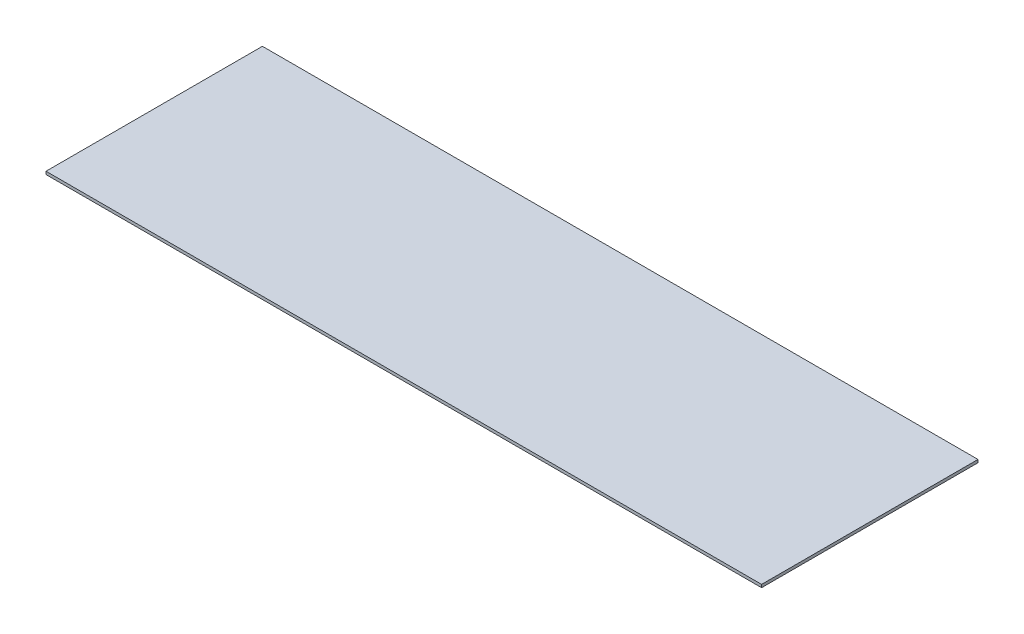
SolidWorks part; units mm, degrees
material "Glas"
ref_plane "Ebene vorne" through (0, 0, 0) normal (0, 0, 1) x (1, 0, 0)
ref_plane "Ebene oben" through (0, 0, 0) normal (0, 1, 0) x (1, 0, 0)
ref_plane "Ebene rechts" through (0, 0, 0) normal (1, 0, 0) x (0, 0, -1)
sketch "Skizze1" plane through (0, 0, 0) normal (0, 0, 1) x (1, 0, 0)
  line L0 (496, 0) -> (-496, 0)
  line L1 (496, 4) -> (-496, 4)
  line L2 (-496, 4) -> (-496, 0)
  line L3 (496, 0) -> (496, 4)
  point P4 (0, 0)
  point P8 (0, 4)
  dimension "D1" = 4
  dimension "D2" = 992
extrude "Aufsatz-Linear austragen1" add sketch "Skizze1" along normal blind 300
equation "\"wall_thickness\"= 4mm"
equation "\"wall_height\"= 300"
equation "\"D1@Skizze1\"=\"wall_thickness\""
equation "\"D1@Aufsatz-Linear austragen1\"=\"wall_height\""
equation "\"edge_length\"= 800mm"
equation "\"coldplate_circumference\"= 4*\"edge_length\""
equation "\"L-profile_width\"= 20mm"
equation "\"L-profile_thickness\"= 1.5mm"
equation "\"extrusion_width\"= 40mm"
equation "\"D2@Skizze1\"=\"edge_length\" + 200 - \"wall_thickness\"*2"
